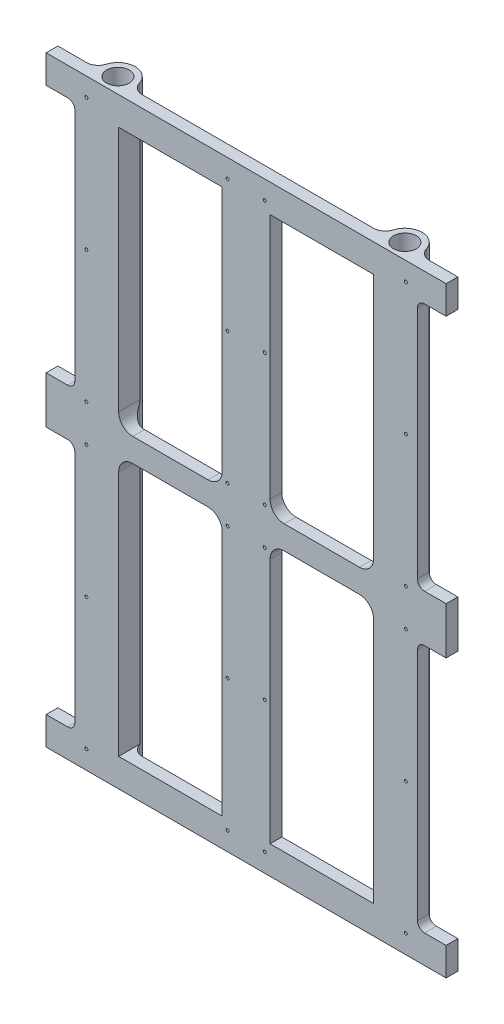
SolidWorks part; units mm, degrees
material "E-Glass Fiber"
ref_plane "Front Plane" through (0, 0, 0) normal (0, 0, 1) x (1, 0, 0)
ref_plane "Top Plane" through (0, 0, 0) normal (0, 1, 0) x (1, 0, 0)
ref_plane "Right Plane" through (0, 0, 0) normal (1, 0, 0) x (0, 0, -1)
other "Center of Mass"
sketch "Sketch1" plane through (0, 0, 0) normal (0, 1, 0) x (1, 0, 0)
  line L19 (85, -5) -> (85, 0)
  line L20 (85, -5) -> (-85, -5)
  line L24 (85, 0) -> (72.8176, 0)
  line L25 (-85, -5) -> (-85, 0)
  line L26 (85, -5) -> (-85, 0) construction
  line L27 (85, 0) -> (-85, -5) construction
  line L28 (0, 0) -> (0, -5) construction
  line L29 (-72.8176, 0) -> (-85, 0)
  line L30 (49.1824, 0) -> (-49.1824, 0)
  circle A29 centre (-61, 1.5) radius 4.825
  arc A30 (-68.1698, 0) -> (-53.8302, 0) centre (-61, 1.5) ccw construction
  arc A31 (-72.8176, 0) -> (-68.0234, 3.5801) centre (-72.8176, 5) ccw
  arc A32 (-53.9766, 3.5801) -> (-49.1824, 0) centre (-49.1824, 5) ccw
  arc A33 (-53.9766, 3.5801) -> (-68.0234, 3.5801) centre (-61, 1.5) ccw
  arc A34 (68.1698, 0) -> (53.8302, 0) centre (61, 1.5) cw construction
  arc A35 (53.9766, 3.5801) -> (68.0234, 3.5801) centre (61, 1.5) cw
  arc A36 (53.9766, 3.5801) -> (49.1824, 0) centre (49.1824, 5) cw
  arc A37 (72.8176, 0) -> (68.0234, 3.5801) centre (72.8176, 5) cw
  circle A38 centre (61, 1.5) radius 4.825
  point P1 (0, -2.5)
  dimension "D3" = 9.65
  dimension "D4" = 6.5
  dimension "D5" = 61
  dimension "D6" = 14.65
  dimension "D1" = 5
  dimension "D2" = 170
extrude "Boss-Extrude1" add sketch "Sketch1" along normal blind 255.6
sketch "Sketch2" plane through (0, 0, 0) normal (0, 0, -1) x (-1, 0, 0)
  line L0 (0, 127.8) -> (-255.8, 127.8) construction
  line L5 (-56.175, 0) -> (-56.175, 550) construction
  line L6 (-54.175, 243.6) -> (-10.175, 243.6)
  line L7 (0, 255.6) -> (-255.8, 255.6) construction
  line L9 (-65.825, 550) -> (-65.825, 0) construction
  line L15 (-54.175, 243.6) -> (-54.175, 138.8)
  line L16 (-48.175, 132.8) -> (-16.175, 132.8)
  line L17 (-87.825, 137.8) -> (-75.825, 137.8)
  line L18 (-10.175, 243.6) -> (-10.175, 138.8)
  line L31 (-54.175, 243.6) -> (-10.175, 132.8) construction
  line L32 (-54.175, 132.8) -> (-10.175, 243.6) construction
  line L33 (-87.825, 12) -> (-72.825, 117.8) construction
  line L35 (-87.825, 137.8) -> (-87.825, 243.6)
  line L36 (-87.825, 243.6) -> (-75.825, 243.6)
  line L37 (-72.825, 140.8) -> (-72.825, 240.6)
  line L38 (-87.825, 137.8) -> (-72.825, 243.6) construction
  line L39 (-87.825, 243.6) -> (-72.825, 137.8) construction
  line L40 (-87.825, 117.8) -> (-72.825, 12) construction
  line L41 (-54.175, 122.8) -> (-10.175, 12) construction
  line L42 (-54.175, 12) -> (-10.175, 122.8) construction
  line L43 (-72.825, 114.8) -> (-72.825, 15)
  line L44 (-87.825, 12) -> (-75.825, 12)
  line L45 (-87.825, 117.8) -> (-87.825, 12)
  line L46 (-10.175, 12) -> (-10.175, 116.8)
  line L47 (-87.825, 117.8) -> (-75.825, 117.8)
  line L48 (-48.175, 122.8) -> (-16.175, 122.8)
  line L49 (-54.175, 12) -> (-54.175, 116.8)
  line L50 (-54.175, 12) -> (-10.175, 12)
  line L51 (0, 255.6) -> (0, 127.8) construction
  line L52 (54.175, 12) -> (10.175, 122.8) construction
  line L53 (54.175, 122.8) -> (10.175, 12) construction
  line L54 (87.825, 117.8) -> (72.825, 12) construction
  line L55 (87.825, 243.6) -> (72.825, 137.8) construction
  line L56 (87.825, 137.8) -> (72.825, 243.6) construction
  line L57 (87.825, 12) -> (72.825, 117.8) construction
  line L58 (54.175, 132.8) -> (10.175, 243.6) construction
  line L59 (54.175, 243.6) -> (10.175, 132.8) construction
  line L60 (54.175, 12) -> (10.175, 12)
  line L61 (54.175, 12) -> (54.175, 116.8)
  line L62 (48.175, 122.8) -> (16.175, 122.8)
  line L63 (87.825, 117.8) -> (75.825, 117.8)
  line L64 (10.175, 12) -> (10.175, 116.8)
  line L65 (87.825, 117.8) -> (87.825, 12)
  line L66 (87.825, 12) -> (75.825, 12)
  line L67 (72.825, 114.8) -> (72.825, 15)
  line L68 (72.825, 140.8) -> (72.825, 240.6)
  line L69 (87.825, 243.6) -> (75.825, 243.6)
  line L70 (87.825, 137.8) -> (87.825, 243.6)
  line L71 (10.175, 243.6) -> (10.175, 138.8)
  line L72 (87.825, 137.8) -> (75.825, 137.8)
  line L73 (48.175, 132.8) -> (16.175, 132.8)
  line L74 (54.175, 243.6) -> (54.175, 138.8)
  line L75 (54.175, 243.6) -> (10.175, 243.6)
  arc A0 (-10.175, 138.8) -> (-16.175, 132.8) centre (-16.175, 138.8) cw
  arc A1 (-54.175, 138.8) -> (-48.175, 132.8) centre (-48.175, 138.8) ccw
  arc A2 (-75.825, 137.8) -> (-72.825, 140.8) centre (-75.825, 140.8) ccw
  arc A3 (-72.825, 240.6) -> (-75.825, 243.6) centre (-75.825, 240.6) ccw
  arc A4 (-72.825, 15) -> (-75.825, 12) centre (-75.825, 15) cw
  arc A5 (-75.825, 117.8) -> (-72.825, 114.8) centre (-75.825, 114.8) cw
  arc A6 (-54.175, 116.8) -> (-48.175, 122.8) centre (-48.175, 116.8) cw
  arc A7 (-10.175, 116.8) -> (-16.175, 122.8) centre (-16.175, 116.8) ccw
  arc A8 (10.175, 116.8) -> (16.175, 122.8) centre (16.175, 116.8) cw
  arc A9 (54.175, 116.8) -> (48.175, 122.8) centre (48.175, 116.8) ccw
  arc A10 (75.825, 117.8) -> (72.825, 114.8) centre (75.825, 114.8) ccw
  arc A11 (72.825, 15) -> (75.825, 12) centre (75.825, 15) ccw
  arc A12 (72.825, 240.6) -> (75.825, 243.6) centre (75.825, 240.6) cw
  arc A13 (75.825, 137.8) -> (72.825, 140.8) centre (75.825, 140.8) cw
  arc A14 (54.175, 138.8) -> (48.175, 132.8) centre (48.175, 138.8) cw
  arc A15 (10.175, 138.8) -> (16.175, 132.8) centre (16.175, 138.8) ccw
  point P0 (-32.175, 188.2)
  point P11 (-80.325, 190.7)
  point P44 (-80.325, 64.9)
  point P45 (-32.175, 67.4)
  point P94 (32.175, 67.4)
  point P95 (80.325, 64.9)
  point P96 (80.325, 190.7)
  point P97 (32.175, 188.2)
  dimension "D8" = 6
  dimension "D9" = 3
  dimension "D1" = 44
  dimension "D2" = 2
  dimension "D3" = 12
  dimension "D4" = 5
  dimension "D5" = 7
  dimension "D6" = 15
  dimension "D7" = 10
extrude "Cut-Extrude2" cut sketch "Sketch2" against normal through all and the other way through all
sketch "Sketch3" plane through (0, 0, 5) normal (0, 0, -1) x (-1, 0, 0)
  line L0 (0, 0) -> (0, 255.6) construction
  line L1 (-49.1824, 0) -> (49.1824, 0) construction
  line L5 (0, 255.6) -> (255.8, 255.6) construction
  line L6 (0, 127.8) -> (-255.8, 127.8) construction
  point P0 (-67.9, 7.9)
  point P1 (-7.9, 7.9)
  point P3 (-7.9, 63.9)
  point P5 (-67.9, 63.9)
  point P7 (-67.9, 119.9)
  point P9 (-7.9, 119.9)
  point P23 (7.9, 119.9)
  point P24 (67.9, 119.9)
  point P25 (67.9, 63.9)
  point P26 (7.9, 63.9)
  point P27 (7.9, 7.9)
  point P28 (67.9, 7.9)
  point P31 (67.9, 503.3)
  point P32 (7.9, 503.3)
  point P33 (7.9, 447.3)
  point P34 (67.9, 447.3)
  point P35 (67.9, 391.3)
  point P36 (7.9, 391.3)
  point P37 (-7.9, 391.3)
  point P38 (-67.9, 391.3)
  point P39 (-67.9, 447.3)
  point P40 (-7.9, 447.3)
  point P41 (-7.9, 503.3)
  point P42 (-67.9, 503.3)
  point P43 (-260.9282, 171.0026)
  point P46 (67.9, 247.7)
  point P47 (7.9, 247.7)
  point P48 (7.9, 191.7)
  point P49 (67.9, 191.7)
  point P50 (67.9, 135.7)
  point P51 (7.9, 135.7)
  point P52 (-7.9, 135.7)
  point P53 (-67.9, 135.7)
  point P54 (-67.9, 191.7)
  point P55 (-7.9, 191.7)
  point P56 (-7.9, 247.7)
  point P57 (-67.9, 247.7)
hole_wizard "Ø1.25 (1.25) Diameter Hole1" positions "Sketch3" profile "Sketch4" hole size "Ø1.25" standard "ANSI Metric" end condition through all
sketch "Sketch4" plane through (67.9, 7.9, 5) normal (1, 0, 0) x (0, -1, 0)
  line L0 (0, 0) -> (0, 13.825)
  line L1 (0, 13.825) -> (0.625, 13.825)
  line L2 (0.625, 13.825) -> (0.625, 0)
  line L5 (0.625, 0) -> (0, 0)
  line L11 (0, -6.35) -> (0, 107.95) construction
  dimension "Thru Hole Dia." = 1.25
  dimension "Thru Hole Depth" = 13.825
sketch "Sketch5" plane through (0, 0, 0) normal (0, 0, -1) x (-1, 0, 0)
  line L2 (0, 255.6) -> (0, 127.8) construction
  line L3 (0, 127.8) -> (-255.8, 127.8) construction
  circle A24 centre (-67.9, 247.7) radius 1.5
  circle A25 centre (-7.9, 247.7) radius 1.5
  circle A26 centre (-67.9, 191.7) radius 1.5
  circle A27 centre (-67.9, 135.7) radius 1.5
  circle A28 centre (-7.9, 135.7) radius 1.5
  circle A29 centre (-7.9, 191.7) radius 1.5
  circle A48 centre (7.9, 191.7) radius 1.5
  circle A49 centre (7.9, 135.7) radius 1.5
  circle A50 centre (67.9, 135.7) radius 1.5
  circle A51 centre (67.9, 191.7) radius 1.5
  circle A52 centre (7.9, 247.7) radius 1.5
  circle A53 centre (67.9, 247.7) radius 1.5
  circle A54 centre (67.9, 7.9) radius 1.5
  circle A55 centre (7.9, 7.9) radius 1.5
  circle A56 centre (67.9, 63.9) radius 1.5
  circle A57 centre (67.9, 119.9) radius 1.5
  circle A58 centre (7.9, 119.9) radius 1.5
  circle A59 centre (7.9, 63.9) radius 1.5
  circle A60 centre (-7.9, 63.9) radius 1.5
  circle A61 centre (-7.9, 119.9) radius 1.5
  circle A62 centre (-67.9, 119.9) radius 1.5
  circle A63 centre (-67.9, 63.9) radius 1.5
  circle A64 centre (-7.9, 7.9) radius 1.5
  circle A65 centre (-67.9, 7.9) radius 1.5
  dimension "D1" = 3
extrude "Cut-Extrude3" cut sketch "Sketch5" along normal through all
equation "\"rod_d\"= 9.65"
equation "\"big_bearing_id\"= 140mm"
equation "\"rod_offset_c2c\"= \"big_bearing_id\" / 2 - \"rod_d\" / 2 - 1.5"
